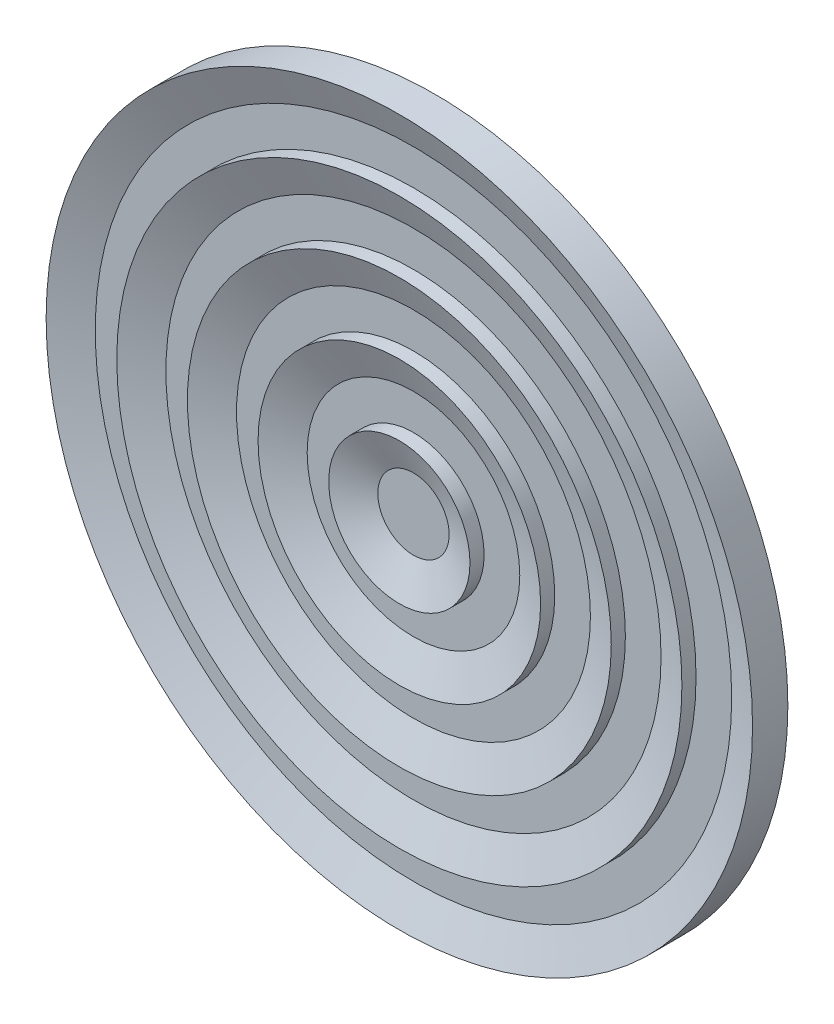
SolidWorks part; units mm, degrees
ref_plane "Plan de face" through (0, 0, 0) normal (0, 0, 1) x (1, 0, 0)
ref_plane "Plan de dessus" through (0, 0, 0) normal (0, 1, 0) x (1, 0, 0)
ref_plane "Plan de droite" through (0, 0, 0) normal (1, 0, 0) x (0, 0, -1)
sketch "Esquisse1" plane through (0, 0, 0) normal (0, 0, 1) x (1, 0, 0)
  circle A0 centre (0, 0) radius 5
extrude "Boss.-Extru.1" add sketch "Esquisse1" along normal blind 0.5
sketch "Esquisse2" plane through (0, 0, 0.5) normal (0, 0, 1) x (1, 0, 0)
  circle A0 centre (0, 0) radius 4.5
  circle A1 centre (0, 0) radius 4
  circle A2 centre (0, 0) radius 3.5
  circle A3 centre (0, 0) radius 3
  circle A4 centre (0, 0) radius 2.5
  circle A5 centre (0, 0) radius 2
  circle A6 centre (0, 0) radius 1.5
  circle A7 centre (0, 0) radius 1
  circle A8 centre (0, 0) radius 0.5
  dimension "D1" = 0.5
  dimension "D2" = 0.5
  dimension "D3" = 0.5
  dimension "D4" = 0.5
  dimension "D5" = 0.5
  dimension "D6" = 0.5
  dimension "D7" = 0.5
  dimension "D8" = 0.5
extrude "Enlèv. mat.-Extru.2" cut sketch "Esquisse2" against normal blind 0.2 contours A8 | A6 A7 | A4 A5 | A2 A3 | A0 A1 region at (-4.3727, 0, 0.5) region at (-3.401, 0, 0.5) region at (-2.4293, 0, 0.5) region at (-1.4576, 0, 0.5) region at (0, 0, 0.5)
chamfer "Chanfrein1" distance 0.5 angle 22 5 edges at (0.5, 0, 0.5) (1.5, 0, 0.5) (2.5, 0, 0.5) (3.5, 0, 0.5) (4.5, 0, 0.5) first distance on face at (0.5, 0, 0.5) first distance on face at (1.5, 0, 0.5) first distance on face at (2.5, 0, 0.5) first distance on face at (3.5, 0, 0.5) first distance on face at (4.5, 0, 0.5)
